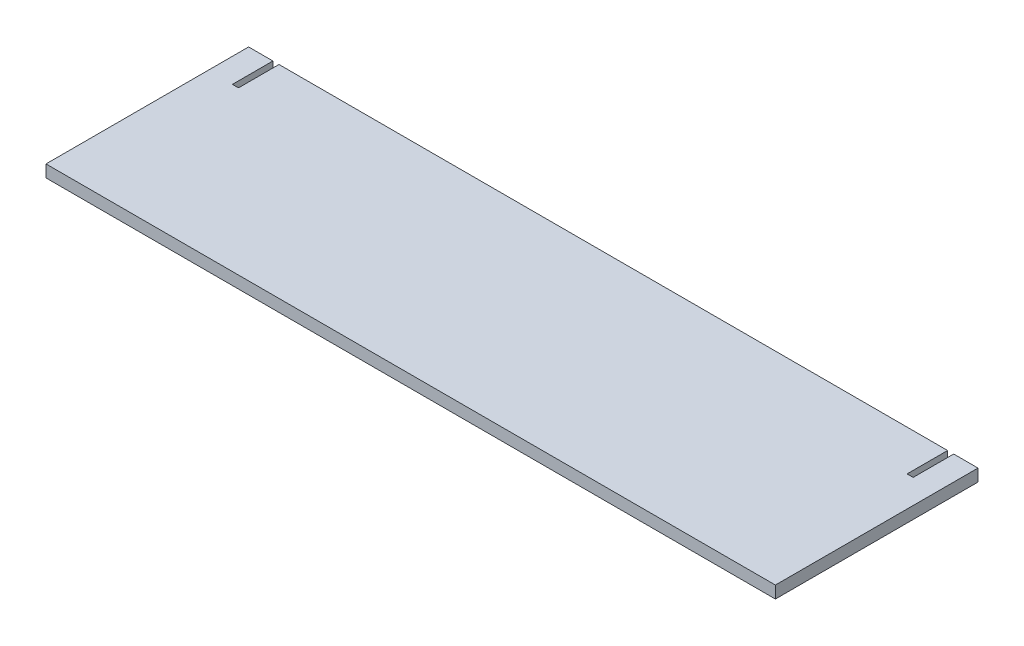
SolidWorks part; units mm, degrees
ref_plane "Front Plane" through (0, 0, 0) normal (0, 0, 1) x (1, 0, 0)
ref_plane "Top Plane" through (0, 0, 0) normal (0, 1, 0) x (1, 0, 0)
ref_plane "Right Plane" through (0, 0, 0) normal (1, 0, 0) x (0, 0, -1)
sketch "Sketch1" plane through (0, 0, 0) normal (0, 1, 0) x (1, 0, 0)
  line L0 (-84, 25) -> (-84, 15)
  line L1 (-90, -25) -> (90, -25)
  line L2 (-90, -25) -> (-90, 25)
  line L3 (-90, 25) -> (-84, 25)
  line L4 (90, -25) -> (90, 25)
  line L5 (-84, 15) -> (-82.5, 15)
  line L6 (-82.5, 15) -> (-82.5, 25)
  line L7 (82.5, 25) -> (82.5, 15)
  line L8 (82.5, 15) -> (84, 15)
  line L9 (84, 15) -> (84, 25)
  line L10 (-82.5, 25) -> (82.5, 25)
  line L11 (84, 25) -> (90, 25)
  point P4 (-90, 0)
  point P5 (0, 25)
  dimension "D1" = 50
  dimension "D2" = 180
  dimension "D3" = 6
  dimension "D4" = 1.5
  dimension "D5" = 10
extrude "Boss-Extrude1" add sketch "Sketch1" along normal mid plane 3
equation "\"mdfWidth\"= 3"
equation "\"cellSide\"= 180"
equation "\"mazeHeight\" = 50"
equation "\"slitHeight\"= 10"
equation "\"slitWidth\" = \"wallThickness\""
equation "\"gripWidth\"= 6"
equation "\"wallThickness\"= 1.5"
equation "\"D1@Sketch1\"= \"mazeHeight\""
equation "\"D2@Sketch1\"= \"cellSide\""
equation "\"D3@Sketch1\"= \"gripWidth\""
equation "\"D4@Sketch1\"= \"wallThickness\""
equation "\"D5@Sketch1\"= \"slitHeight\""
equation "\"D1@Boss-Extrude1\"= \"mdfWidth\""
